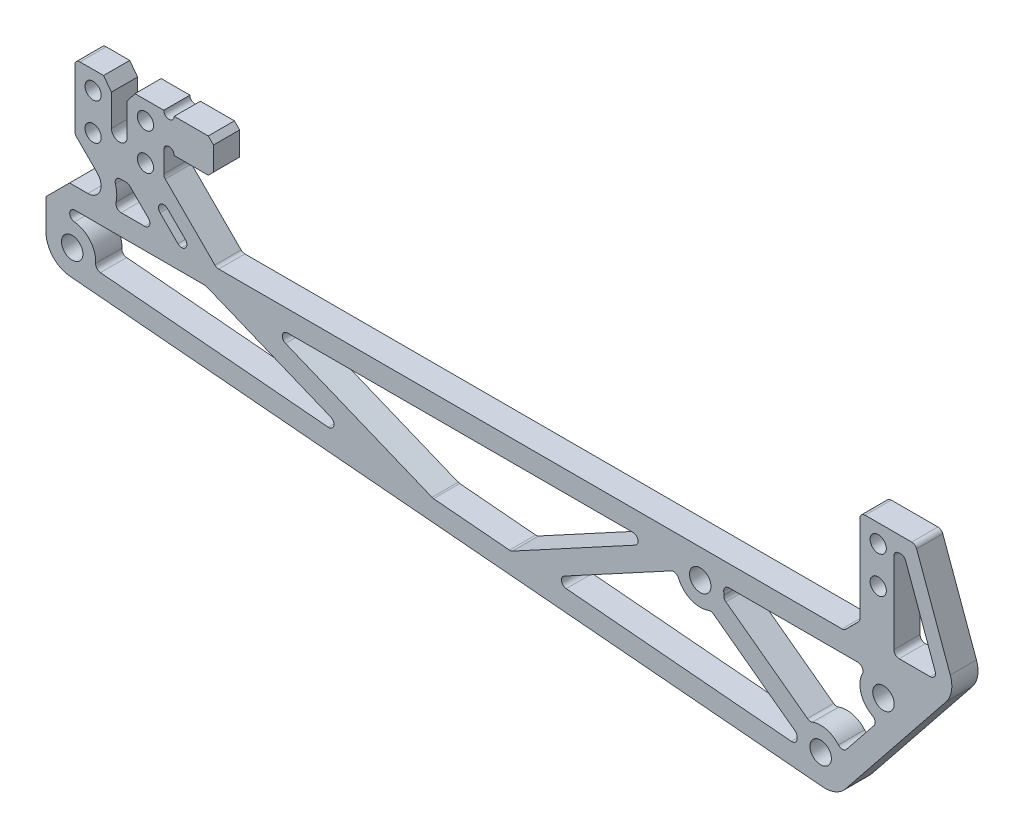
SolidWorks part; units mm, degrees
ref_plane "前视基准面" through (0, 0, 0) normal (0, 0, 1) x (1, 0, 0)
ref_plane "上视基准面" through (0, 0, 0) normal (0, 1, 0) x (1, 0, 0)
ref_plane "右视基准面" through (0, 0, 0) normal (1, 0, 0) x (0, 0, -1)
sketch "草图1" plane through (0, 0, 0) normal (0, 0, 1) x (1, 0, 0)
  line L0 (145, 3.5) -> (145, -3.5) construction
  line L1 (5, -3.5) -> (-5, -3.5) construction
  line L2 (5, -3.5) -> (5, 3.5) construction
  line L3 (5, 3.5) -> (-5, 3.5) construction
  line L4 (-5, -3.5) -> (-5, 3.5) construction
  line L5 (5, -3.5) -> (-5, 3.5) construction
  line L6 (5, 3.5) -> (-5, -3.5) construction
  line L7 (-6, -14.025) -> (-14, -14.025)
  line L8 (-14, -14.025) -> (-14, -29.025)
  line L9 (-14, -29.025) -> (171.1071, -45.2198)
  line L10 (171.1071, -45.2198) -> (152.1006, 7)
  line L11 (-6, -8.975) -> (-8.5, -8.975)
  line L12 (-8.5, -8.975) -> (-8.5, 7)
  line L13 (-8.5, 7) -> (8.5, 7)
  line L14 (8.5, 7) -> (8.5, -14.025)
  line L15 (8.5, -14.025) -> (141.5, -14.025)
  line L16 (141.5, -14.025) -> (141.5, 7)
  line L17 (141.5, 7) -> (152.1006, 7)
  line L18 (148, 4) -> (148, -13.5)
  line L19 (148, -13.5) -> (156.3695, -13.5)
  line L20 (156.3695, -13.5) -> (150, 4)
  line L21 (150, 4) -> (148, 4)
  circle A0 centre (-5, 3.5) radius 1.55
  circle A1 centre (5, 3.5) radius 1.55
  circle A2 centre (-5, -3.5) radius 1.55
  circle A3 centre (5, -3.5) radius 1.55
  circle A4 centre (145, 3.5) radius 1.55
  circle A5 centre (145, -3.5) radius 1.55
  arc A6 (-6, -14.025) -> (-6, -8.975) centre (-6, -11.5) ccw
  point P0 (0, 0)
  dimension "D3" = 3.1
  dimension "D4" = 140
  dimension "D5" = 1
  dimension "D6" = 8
  dimension "D7" = 5.05
  dimension "D12" = 3.5
  dimension "D1" = 7
  dimension "D2" = 10
  dimension "D8" = 3.5
  dimension "D9" = 3.5
  dimension "D10" = 3.5
  dimension "D11" = 3.5
  dimension "D13" = 3
  dimension "D14" = 3
  dimension "D15" = 3
  dimension "D16" = 10
  dimension "D17" = 2
  dimension "D18" = 70
  dimension "D19" = 8
  dimension "D20" = 15
  dimension "D21" = 5
extrude "凸台-拉伸1" add sketch "草图1" along normal mid plane 5
fillet "圆角1" radius 1 6 edges at (148, 4, 0) (152.1006, 7, 0) (141.5, 7, 0) (156.3695, -13.5, 0) (148, -13.5, 0) (150, 4, 0)
chamfer "倒角1" distance 3 angle 45 2 edges at (141.5, -14.025, 0) (8.5, -14.025, 0)
sketch "草图3" plane through (0, 0, 2.5) normal (0, 0, 1) x (1, 0, 0)
  circle A0 centre (-9, -24.5) radius 2.05
  circle A1 centre (-5, -3.5) radius 1.55 construction
  circle A2 centre (146, -21.5) radius 2.05
  circle A3 centre (134, -36.5) radius 2.05
  dimension "D1" = 21
  dimension "D2" = 4.1
  dimension "D3" = 4
  dimension "D4" = 155
  dimension "D5" = 3
  dimension "D6" = 15
  dimension "D7" = 12
extrude "切除-拉伸1" cut sketch "草图3" against normal through all
sketch "草图4" plane through (0, 0, 2.5) normal (0, 0, 1) x (1, 0, 0)
  line L0 (159.7252, -13.9482) -> (137.0889, -42.2436)
  line L1 (171.1071, -45.2198) -> (152.3401, 6.342) construction
  line L2 (-14, -29.025) -> (171.1071, -45.2198) construction
  line L3 (134, -36.5) -> (146, -21.5) construction
  line L4 (159.7252, -13.9482) -> (171.1071, -45.2198)
  line L5 (171.1071, -45.2198) -> (137.0889, -42.2436)
  dimension "D1" = 6
extrude "切除-拉伸2" cut sketch "草图4" against normal through all
sketch "草图5" plane through (0, 0, 2.5) normal (0, 0, 1) x (1, 0, 0)
  line L0 (-12.182, -21.318) -> (-8.889, -18.025)
  line L1 (-8.889, -18.025) -> (143.1409, -18.025)
  line L2 (138.5, -14.025) -> (11.5, -14.025) construction
  line L3 (138.08, -34.6016) -> (145.0435, -25.8972)
  line L4 (159.7252, -13.9482) -> (137.0889, -42.2436) construction
  line L5 (129.6305, -37.5758) -> (-4.699, -25.8235)
  line L6 (-14, -29.025) -> (137.0889, -42.2436) construction
  arc A0 (-4.699, -25.8235) -> (-12.182, -21.318) centre (-9, -24.5) ccw
  arc A1 (138.08, -34.6016) -> (129.6305, -37.5758) centre (134, -36.5) ccw
  arc A2 (143.1409, -18.025) -> (145.0435, -25.8972) centre (146, -21.5) ccw
  dimension "D1" = 4.5
  dimension "D2" = 45
  dimension "D3" = 4
  dimension "D4" = 4
  dimension "D5" = 4
extrude "切除-拉伸3" cut sketch "草图5" against normal through all
fillet "圆角2" radius 1 7 edges at (143.1409, -18.025, 0) (145.0435, -25.8972, 0) (138.08, -34.6016, 0) (129.6305, -37.5758, 0) (-4.699, -25.8235, 0) (-12.182, -21.318, 0) (-8.889, -18.025, 0)
chamfer "倒角2" distance 4.5 angle 45 1 edges at (-14, -14.025, 0)
fillet "圆角4" radius 5 3 edges at (159.7252, -13.9482, 0) (137.0889, -42.2436, 0) (-14, -29.025, 0)
sketch "草图7" plane through (0, 0, 2.5) normal (0, 0, 1) x (1, 0, 0)
  line L0 (16.5253, -18.025) -> (46.4837, -30.3014)
  line L1 (141.0883, -18.025) -> (-8.4747, -18.025) construction
  line L2 (-3.6035, -25.9193) -> (128.4129, -37.4692) construction
  line L3 (27.0744, -18.025) -> (59.8965, -31.4748)
  line L4 (102.0744, -18.025) -> (74.8394, -32.7822)
  line L5 (110.4706, -18.025) -> (82.0684, -33.4146)
  line L6 (16.5253, -18.025) -> (27.0744, -18.025)
  line L7 (46.4837, -30.3014) -> (59.8965, -31.4748)
  line L8 (102.0744, -18.025) -> (110.4706, -18.025)
  line L9 (74.8394, -32.7822) -> (82.0684, -33.4146)
  arc A0 (-4.5133, -24.8462) -> (-3.6035, -25.9193) centre (-3.5163, -24.9231) ccw construction
  dimension "D1" = 4
  dimension "D2" = 4
  dimension "D3" = 75
  dimension "D4" = 15
  dimension "D5" = 50
  dimension "D6" = 25
extrude "凸台-拉伸3" add sketch "草图7" against normal up to surface (5 mm away) up to face at (75.7719, -25.2729, -2.5)
fillet "圆角5" radius 1 8 edges at (46.4837, -30.3014, 0) (16.5253, -18.025, 0) (27.0744, -18.025, 0) (59.8965, -31.4748, 0) (74.8394, -32.7822, 0) (102.0744, -18.025, 0) (110.4706, -18.025, 0) (82.0684, -33.4146, 0)
fillet "圆角7" radius 1 2 edges at (8.5, 7, 0) (-8.5, 7, 0)
sketch "草图8" plane through (0, 0, 2.5) normal (0, 0, 1) x (1, 0, 0)
  line L0 (1.7324, -8.5) -> (7.2574, -14.025)
  line L1 (7.2574, -14.025) -> (-1.0857, -14.025)
  line L3 (16.3283, -18.025) -> (-8.4747, -18.025) construction
  line L4 (11.5, -14.025) -> (8.5, -11.025) construction
  line L5 (1.7324, -8.5) -> (-1.3604, -8.5)
  arc A0 (-1.0857, -14.025) -> (-1.3604, -8.5) centre (-6, -11.5) ccw
  arc A1 (-6, -14.025) -> (-6, -8.975) centre (-6, -11.5) ccw construction
  circle A2 centre (-5, -3.5) radius 1.55 construction
  dimension "D1" = 3
  dimension "D2" = 4
  dimension "D3" = 3
  dimension "D4" = 5
extrude "切除-拉伸4" cut sketch "草图8" against normal through all
fillet "圆角8" radius 1 4 edges at (7.2574, -14.025, 0) (1.7324, -8.5, 0) (-1.0857, -14.025, 0) (-1.3604, -8.5, 0)
sketch "草图9" plane through (0, 0, 2.5) normal (0, 0, 1) x (1, 0, 0)
  line L0 (8.5, -11.025) -> (7.0858, -9.6108)
  line L1 (7.0858, -9.6108) -> (8.5, -8.1966)
  line L2 (8.5, -11.025) -> (8.5, 6) construction
  line L3 (11.5, -14.025) -> (8.5, -11.025) construction
  line L4 (8.5, -8.1966) -> (8.5, -11.025)
  dimension "D1" = 2
extrude "切除-拉伸5" cut sketch "草图9" against normal through all
sketch "草图10" plane through (0, 0, 2.5) normal (0, 0, 1) x (1, 0, 0)
  line L0 (8.5, -8.1966) -> (14.3284, -14.025)
  line L1 (138.5, -14.025) -> (11.5, -14.025) construction
  line L2 (14.3284, -14.025) -> (18.5711, -14.025)
  line L3 (18.5711, -14.025) -> (8.5, -3.9539)
  line L6 (11.5, -14.025) -> (7.0858, -9.6108) construction
  line L7 (8.5, -8.1966) -> (8.5, -3.9539)
  line L9 (8.5, -8.1966) -> (8.5, 6) construction
  dimension "D1" = 3
extrude "凸台-拉伸5" add sketch "草图10" against normal up to surface (5 mm away) contours L0 L2 L3 L7
sketch "草图11" plane through (0, 0, 2.5) normal (0, 0, 1) x (1, 0, 0)
  line L0 (-4.2146, -9.7146) -> (-8.5, -5.4291)
  line L1 (-8.5, 6) -> (-8.5, -8.975) construction
  line L2 (8.5, -8.1966) -> (14.3284, -14.025) construction
  line L3 (-8.5, -8.975) -> (-6, -8.975) construction
  line L4 (-8.5, -5.4291) -> (-8.5, -8.975)
  line L5 (-8.5, -8.975) -> (-6, -8.975)
  arc A0 (-6, -14.025) -> (-6, -8.975) centre (-6, -11.5) ccw construction
  arc A1 (-4.2146, -9.7146) -> (-6, -8.975) centre (-6, -11.5) ccw
extrude "切除-拉伸6" cut sketch "草图11" against normal through all
fillet "圆角9" radius 1 9 edges at (8.5, -3.9539, 0) (18.5711, -14.025, 0) (14.3284, -14.025, 0) (11.5, -14.025, 0) (138.5, -14.025, 0) (7.0858, -9.6108, 0) (8.5, -8.1966, 0) (-8.5, -5.4291, 0) (141.5, -11.025, 0)
sketch "草图12" plane through (0, 0, 2.5) normal (0, 0, 1) x (1, 0, 0)
  line L0 (-3, 7) -> (-1.5, 5)
  line L1 (7.5, 7) -> (-7.5, 7) construction
  line L2 (-1.5, 5) -> (-1.5, -1)
  line L3 (1.5, -1) -> (1.5, 5)
  line L4 (1.5, 5) -> (3, 7)
  line L5 (3, 7) -> (-3, 7)
  arc A0 (-1.5, -1) -> (1.5, -1) centre (0, -1) ccw
  point P9 (0, 7)
  dimension "D1" = 1.5
  dimension "D2" = 1
  dimension "D3" = 6
  dimension "D4" = 2
extrude "切除-拉伸7" cut sketch "草图12" against normal through all
sketch "草图13" plane through (0, 0, 2.5) normal (0, 0, 1) x (1, 0, 0)
  circle A0 centre (111, -19.5) radius 2.05
  circle A1 centre (146, -21.5) radius 2.05 construction
  circle A2 centre (111, -19.5) radius 4.5
  dimension "D1" = 35
  dimension "D2" = 9
  dimension "D3" = 2
extrude "凸台-拉伸6" add sketch "草图13" against normal up to surface (5 mm away)
fillet "圆角10" radius 1 1 edges at (106.5473, -20.1508, 0)
sketch "草图15" plane through (0, 0, 2.5) normal (0, 0, 1) x (1, 0, 0)
  line L0 (111, -19.5) -> (134, -36.5) construction
  line L1 (113.053, -23.5044) -> (129.5695, -35.7123)
  line L2 (115.4305, -20.2877) -> (131.947, -32.4956)
  line L3 (112.1888, -17.8916) -> (135.1888, -34.8916) construction
  line L4 (109.8112, -21.1084) -> (132.8112, -38.1084) construction
  arc A0 (137.4032, -33.5558) -> (129.5001, -36.4779) centre (134, -36.5) ccw construction
  arc A1 (106.8492, -21.2381) -> (115.2514, -18.025) centre (111, -19.5) ccw construction
  arc A2 (131.947, -32.4956) -> (129.5695, -35.7123) centre (134, -36.5) ccw
  arc A3 (113.053, -23.5044) -> (115.4305, -20.2877) centre (111, -19.5) ccw
  dimension "D1" = 2
  dimension "D2" = 2
extrude "凸台-拉伸7" add sketch "草图15" against normal up to surface (5 mm away)
fillet "圆角11" radius 1 5 edges at (131.947, -32.4956, 0) (115.4305, -20.2877, 0) (129.5695, -35.7123, 0) (113.053, -23.5044, 0) (115.2514, -18.025, 0)
sketch "草图16" plane through (0, 0, 2.5) normal (0, 0, 1) x (1, 0, 0)
  line L0 (7.5, 7) -> (18, 7)
  line L1 (18, 7) -> (18, 0.5)
  line L2 (18, 0.5) -> (8.5, 0.5)
  line L3 (8.5, -3.5397) -> (8.5, 6) construction
  line L4 (8.5, 0.5) -> (8.5, 6)
  arc A0 (8.5, 6) -> (7.5, 7) centre (7.5, 6) ccw construction
  arc A1 (8.5, 6) -> (7.5, 7) centre (7.5, 6) ccw
  circle A2 centre (5, 3.5) radius 1.55 construction
  dimension "D1" = 13
  dimension "D2" = 6.5
extrude "凸台-拉伸8" add sketch "草图16" against normal up to surface (5 mm away)
sketch "草图17" plane through (0, 0, 2.5) normal (0, 0, 1) x (1, 0, 0)
  line L0 (8.5, 0.5) -> (18, 0.5) construction
  line L1 (18, 7) -> (3, 7) construction
  line L2 (9.5, 7) -> (9.5, 0.5) construction
  circle A0 centre (9.5, 0.5) radius 1
  circle A1 centre (9.5, 7) radius 1
  dimension "D1" = 2
extrude "切除-拉伸9" cut sketch "草图17" against normal through all
chamfer "倒角3" distance 1 angle 45 2 edges at (18, 0.5, 0) (18, 7, 0)
sketch "草图18" plane through (0, 0, 2.5) normal (0, 0, 1) x (1, 0, 0)
  circle A0 centre (111, -19.5) radius 2.05
extrude "切除-拉伸10" cut sketch "草图18" against normal through all
